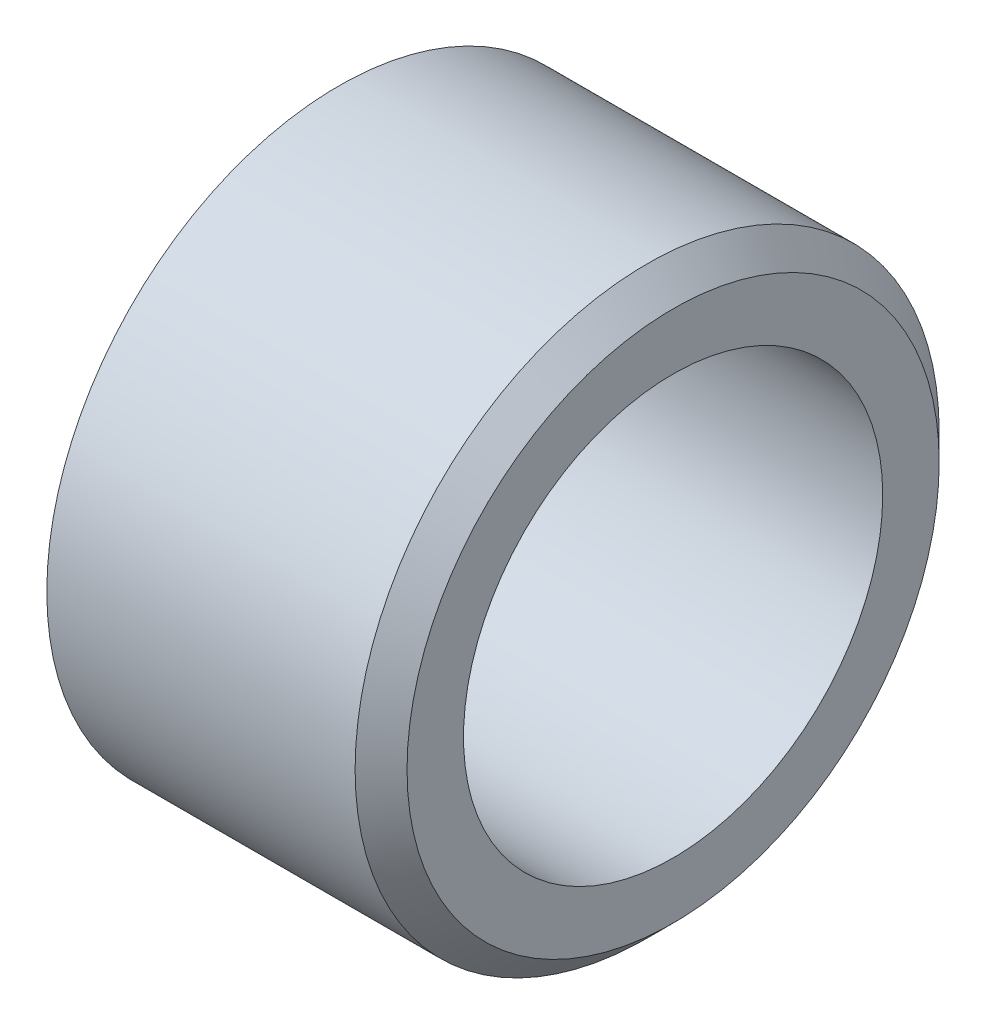
SolidWorks part; units mm, degrees
material "7075-T6 (SN)"
ref_plane "Top" through (0, 0, 0) normal (0, 0, 1) x (1, 0, 0)
ref_plane "Right" through (0, 0, 0) normal (0, 1, 0) x (1, 0, 0)
ref_plane "Front" through (0, 0, 0) normal (1, 0, 0) x (0, 0, -1)
ref_axis "Front Shock Tab Hole Axis" through (-10.541, 219.6337, 542.1263) along (-1, 0, 0)
ref_plane "Plane1" through (0, 219.6337, 0) normal (0, 1, 0) x (1, 0, 0)
sketch "Sketch1" plane through (0, 219.6337, 0) normal (0, 1, 0) x (1, 0, 0)
  line L0 (-4, -542.1263) -> (-4, -536.9193)
  line L1 (-10.541, -542.1263) -> (-4, -542.1263)
  line L2 (-4, -547.2498) -> (-4, -537.0028) construction
  line L3 (-10.541, -546.2284) -> (-10.541, -538.0242) construction
  line L4 (-10.541, -542.1263) -> (-10.541, -536.4113)
  line L6 (-4, -536.9193) -> (-4.508, -536.4113)
  line L11 (-4.508, -536.4113) -> (-10.541, -536.4113)
  line L12 (-10.541, -542.1263) -> (-12.065, -542.1263) construction
  dimension "D1" = 5.207
  dimension "D2" = 5.715
  dimension "D3" = 45
revolve "Revolve1" add sketch "Sketch1" angle 360 about L1
hole_wizard "P (0.323) Diameter Hole1" positions "Sketch2" profile "Sketch3" hole size "P" standard "ANSI Inch" end condition through all
sketch "Sketch2" plane through (-4, 0, 0) normal (1, 0, 0) x (0, 0, -1)
  point P0 (-542.1263, 219.6337)
sketch "Sketch3" plane through (-4, 219.6337, 542.1263) normal (0, 1, 0) x (0, 0, -1)
  line L0 (0, 0) -> (0, 6.541)
  line L1 (0, 6.541) -> (4.1021, 6.541)
  line L2 (4.1021, 6.541) -> (4.1021, 0)
  line L5 (4.1021, 0) -> (0, 0)
  line L11 (0, -6.35) -> (0, 107.95) construction
  dimension "Thru Hole Dia." = 8.2042
  dimension "Thru Hole Depth" = 6.541
